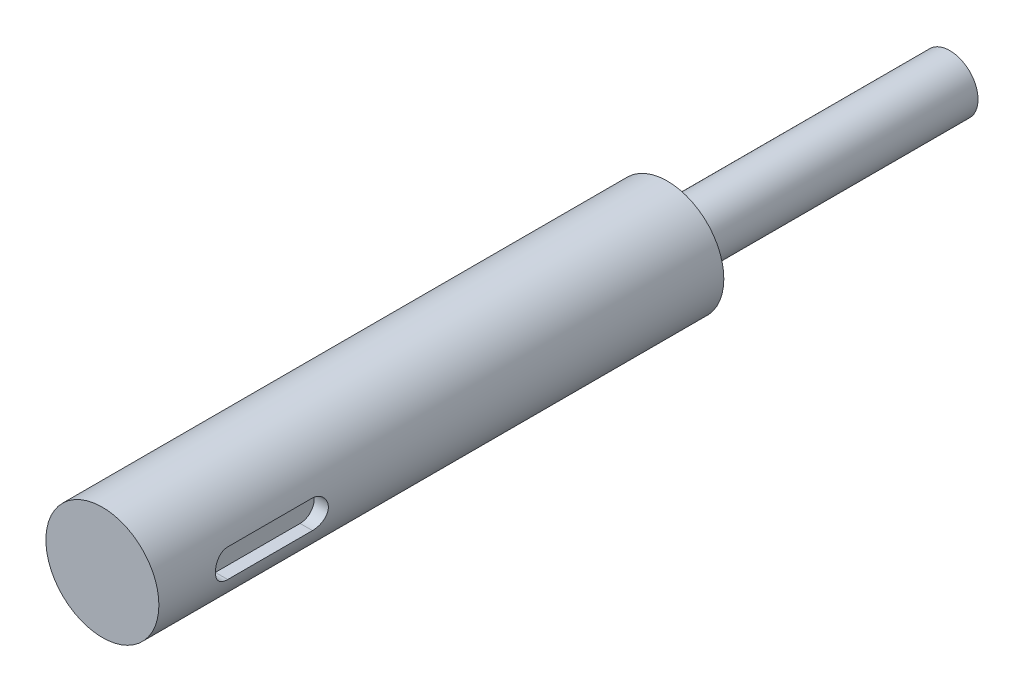
SolidWorks part; units mm, degrees
ref_plane "正面" through (0, 0, 0) normal (0, 0, 1) x (1, 0, 0)
ref_plane "平面" through (0, 0, 0) normal (0, 1, 0) x (1, 0, 0)
ref_plane "右側面" through (0, 0, 0) normal (1, 0, 0) x (0, 0, -1)
sketch "ｽｹｯﾁ1" plane through (0, 0, 0) normal (0, 0, 1) x (1, 0, 0)
  circle A0 centre (0, 0) radius 4
  dimension "D1" = 8
extrude "ﾎﾞｽ - 押し出し1" add sketch "ｽｹｯﾁ1" along normal blind 40
sketch "ｽｹｯﾁ2" plane through (0, 0, 0) normal (0, 0, -1) x (-1, 0, 0)
  circle A0 centre (0, 0) radius 2
  dimension "D1" = 4
extrude "ﾎﾞｽ - 押し出し2" add sketch "ｽｹｯﾁ2" along normal blind 20
ref_plane "平面1" through (3, 0, 0) normal (1, 0, 0) x (0, 0, -1)
sketch "ｽｹｯﾁ3" plane through (3, 0, 0) normal (1, 0, 0) x (0, 0, -1)
  line L0 (0, 0) -> (-40.5336, 0) construction
  line L1 (-35, 0) -> (-29, 0) construction
  line L2 (-35, 1) -> (-29, 1)
  line L3 (-35, -1) -> (-29, -1)
  line L4 (-40, 4) -> (-40, -4) construction
  arc A0 (-35, 1) -> (-35, -1) centre (-35, 0) ccw
  arc A1 (-29, -1) -> (-29, 1) centre (-29, 0) ccw
  point P5 (-32, 0)
  dimension "D1" = 1
  dimension "D2" = 6
  dimension "D3" = 5
extrude "ｶｯﾄ - 押し出し1" cut sketch "ｽｹｯﾁ3" along normal through all
